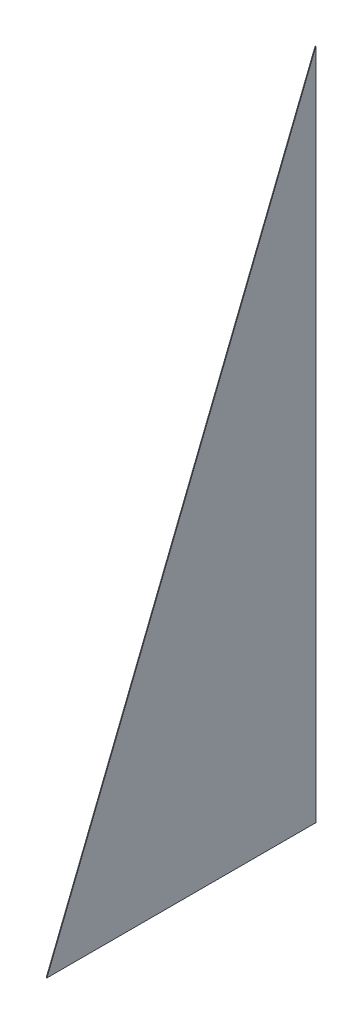
SolidWorks part; units mm, degrees
ref_plane "Front Plane" through (0, 0, 0) normal (0, 0, 1) x (1, 0, 0)
ref_plane "Top Plane" through (0, 0, 0) normal (0, 1, 0) x (1, 0, 0)
ref_plane "Right Plane" through (0, 0, 0) normal (1, 0, 0) x (0, 0, -1)
sketch "Sketch1" plane through (0, 0, 0) normal (1, 0, 0) x (0, 0, -1)
  line L0 (0, 0) -> (0, 1000)
  line L1 (0, 1000) -> (-400, 0)
  line L2 (-400, 0) -> (0, 0)
  dimension "D1" = 1000
  dimension "D2" = 400
extrude "Boss-Extrude1" add sketch "Sketch1" along normal blind 1
